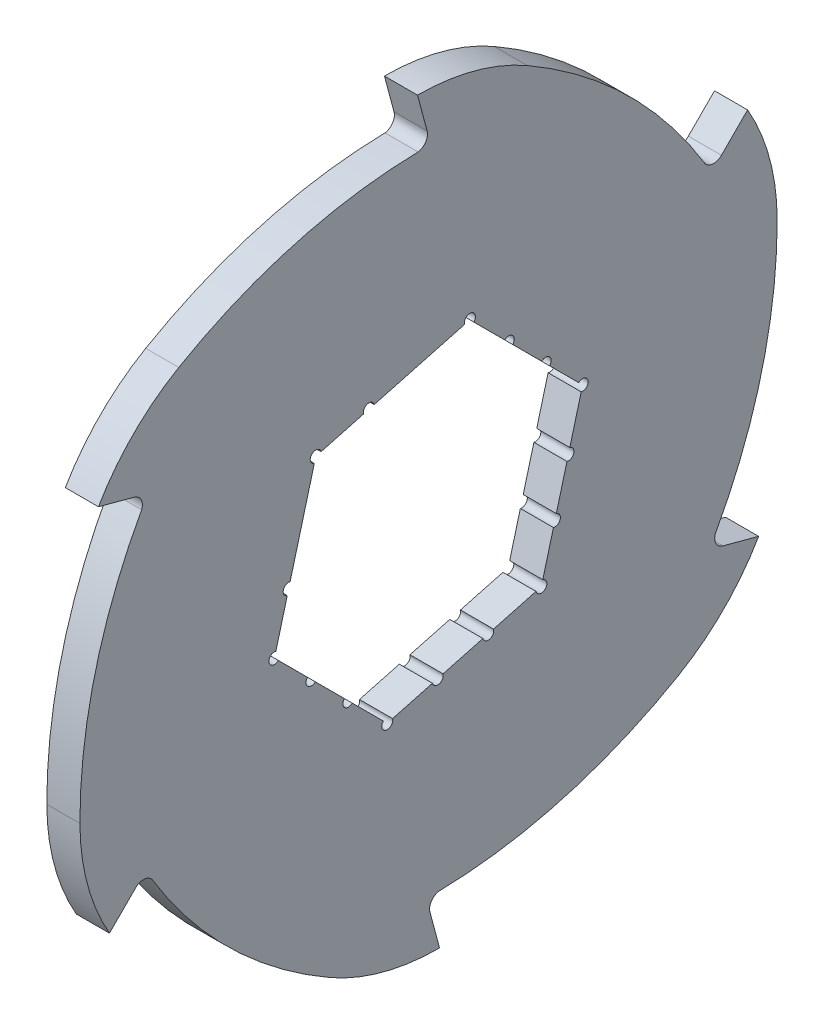
SolidWorks part; units mm, degrees
note: '?' marks a value the reader was unsure of.
material "1.0037 (S235JR)"
ref_plane "Alzado" through (0, 0, 0) normal (0, 0, 1) x (1, 0, 0)
ref_plane "Planta" through (0, 0, 0) normal (0, 1, 0) x (1, 0, 0)
ref_plane "Vista lateral" through (0, 0, 0) normal (1, 0, 0) x (0, 0, -1)
sketch "Sketch1" plane through (0, 0, 0) normal (1, 0, 0) x (0, 0, -1)
  line L0 (-56.6126, 0) -> (65.57, 0) construction
  line L1 (27.9396, 7.4864) -> (7.4864, 27.9396)
  line L2 (7.4864, 27.9396) -> (-20.4532, 20.4532)
  line L3 (-20.4532, 20.4532) -> (-27.9396, -7.4864)
  line L4 (-27.9396, -7.4864) -> (-7.4864, -27.9396)
  line L5 (-7.4864, -27.9396) -> (20.4532, -20.4532)
  line L6 (20.4532, -20.4532) -> (27.9396, 7.4864)
  circle A0 centre (0, 0) radius 25.05 construction
  circle A1 centre (0, 0) radius 59
  dimension "D2" = 118
  dimension "D1" = 50.1
  dimension "D3" = 45
extrude "Extrude1" add sketch "Sketch1" along normal mid plane 6
ref_axis "Axis1" through (-5.5, 0, 0) along (1, 0, 0)?
sketch "Sketch2" plane through (0, 0, 0) normal (1, 0, 0) x (0, 0, -1)
  line L0 (-2, 67.9618) -> (-0.2627, 61.4781)
  line L1 (0, 0) -> (0, 77.6328) construction
  line L4 (-2.1226, 58.9618) -> (0, 0) construction
  circle A0 centre (0, 0) radius 59 construction
  arc A1 (-2, 67.9618) -> (17.9271, 62.6448) centre (-2, 27.9618) cw
  arc A3 (51.2137, 29.2943) -> (-2.1226, 58.9618) centre (0, 0) ccw
  arc A4 (-0.2627, 61.4781) -> (-2.1226, 58.9618) centre (-2.1946, 60.9605) cw
  arc A5 (17.9271, 62.6448) -> (51.2137, 29.2943) centre (-26.9089, -15.3919) cw
  point P10 (-2, 67.9618)
  dimension "D2" = 40
  dimension "D4" = 2
  dimension "D3" = 9
  dimension "D6" = 90
  dimension "D1" = 15
  dimension "D5" = 2
extrude "Extrude2" add sketch "Sketch2" against normal mid plane 6
fillet "Fillet1" [suppressed] radius 0.6
pattern_circular "CirPattern1" count 6 over 360 about axis through (0, 0, 0) along (1, 0, 0) of "Extrude2", "Fillet1"
sketch "Sketch4" [suppressed] plane through (3, 0, 0) normal (1, 0, 0) x (0, 0, -1)
  circle A0 centre (0, 0) radius 67.9646 construction
  dimension "D1" = 135.9291
hole_wizard "Ø2.0 (2) Diameter Hole1" positions "Sketch5" profile "Sketch7" hole size "Ø2.0" standard "ISO" end condition up to next
sketch "Sketch5" plane through (3, 0, 0) normal (1, 0, 0) x (0, 0, -1)
  point P0 (7.4864, 27.9396)
  point P7 (27.9396, 7.4864)
  point P8 (20.4532, -20.4532)
  point P9 (-7.4864, -27.9396)
  point P10 (-27.9396, -7.4864)
  point P11 (-20.4532, 20.4532)
  dimension "D1" = 6
sketch "Sketch7" plane through (3, 27.9396, -7.4864) normal (0, 1, 0) x (0, 0, -1)
  line L0 (0, 0) -> (0, 6)
  line L1 (0, 6) -> (1, 6)
  line L2 (1, 6) -> (1, 0)
  line L5 (1, 0) -> (0, 0)
  line L11 (0, -6.35) -> (0, 107.95) construction
  dimension "Diámetro de taladro hasta el siguiente" = 2
  dimension "Profundidad de taladro hasta el siguiente" = 6
hole_wizard "Ø2.0 (2) Diameter Hole3" positions "Sketch10" profile "Sketch11" hole size "Ø2.0" standard "ISO" end condition up to next
sketch "Sketch10" plane through (3, 0, 0) normal (1, 0, 0) x (0, 0, -1)
  line L0 (8.1935, 27.2325) -> (14.5399, 20.8862) construction
  line L1 (27.2325, 8.1935) -> (8.1935, 27.2325) construction
  line L2 (14.5399, 20.8862) -> (20.8862, 14.5399) construction
  line L3 (20.8862, 14.5399) -> (27.2325, 8.1935) construction
  point P2 (14.5399, 20.8862)
sketch "Sketch11" plane through (3, 20.8862, -14.5399) normal (0, 1, 0) x (0, 0, -1)
  line L0 (0, 0) -> (0, 6.001)
  line L1 (0, 6.001) -> (1, 6.001)
  line L2 (1, 6.001) -> (1, 0)
  line L5 (1, 0) -> (0, 0)
  line L11 (0, -6.35) -> (0, 107.95) construction
  dimension "Diámetro de taladro hasta el siguiente" = 2
  dimension "Profundidad de taladro hasta el siguiente" = 6.001
hole_wizard "Ø2.0 (2) Diameter Hole4" positions "Sketch12" profile "Sketch13" hole size "Ø2.0" standard "ISO" end condition up to next
sketch "Sketch12" plane through (3, 0, 0) normal (1, 0, 0) x (0, 0, -1)
  line L0 (27.2325, 8.1935) -> (15.247, 20.1791) construction
  point P0 (21.2397, 14.1863)
sketch "Sketch13" plane through (3, 14.1863, -21.2397) normal (0, 1, 0) x (0, 0, -1)
  line L0 (0, 0) -> (0, 6.001)
  line L1 (0, 6.001) -> (1, 6.001)
  line L2 (1, 6.001) -> (1, 0)
  line L5 (1, 0) -> (0, 0)
  line L11 (0, -6.35) -> (0, 107.95) construction
  dimension "Diámetro de taladro hasta el siguiente" = 2
  dimension "Profundidad de taladro hasta el siguiente" = 6.001
pattern_circular "CirPattern2" count 6 every 60 about axis through (0, 0, 0) along (1, 0, 0) of "Ø2.0 (2) Diameter Hole3"
pattern_circular "CirPattern3" count 4 every 60 about axis through (0, 0, 0) along (1, 0, 0) of "Ø2.0 (2) Diameter Hole4"
equation "\"D1@Extrude2\"=\"D1@Extrude1\""
